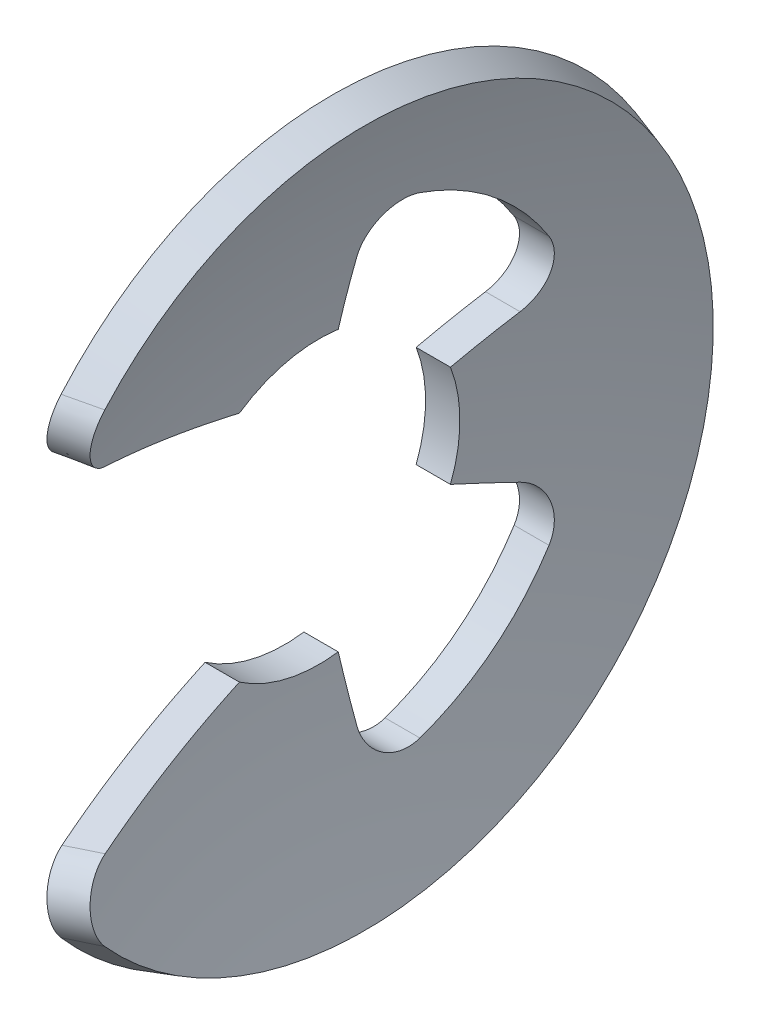
SolidWorks part; units mm, degrees
material "Cast Carbon Steel"
ref_plane "Front" through (0, 0, 0) normal (0, 0, 1) x (1, 0, 0)
ref_plane "Top" through (0, 0, 0) normal (0, 1, 0) x (1, 0, 0)
ref_plane "Right" through (0, 0, 0) normal (1, 0, 0) x (0, 0, -1)
sketch "Sketch2" plane through (0, 0, 0) normal (0, 1, 0) x (1, 0, 0)
  line L0 (0.4113, 6.6929) -> (1.016, 6.4991)
  line L1 (0, 0) -> (-0.635, 0)
  line L2 (1.016, 6.4991) -> (21.2946, 0) construction
  line L3 (0, 0) -> (21.2946, 0) construction
  arc A0 (0, 0) -> (1.016, 6.4991) centre (21.2946, 0) cw
  arc A1 (-0.635, 0) -> (0.4113, 6.6929) centre (21.2946, 0) cw
  dimension "OD" = 13.3858
revolve "Revolve1" add sketch "Sketch2" angle 360 about L3
ref_plane "Plane1" through (1.016, 0, 0) normal (1, 0, 0) x (0, 0, -1)
sketch "Sketch1" plane through (1.016, 0, 0) normal (1, 0, 0) x (0, 0, -1)
  line L0 (-5.7119, -3.4884) -> (-1.4819, -2.1714)
  line L1 (-5.7119, 3.4884) -> (-1.4819, 2.1714)
  line L2 (0.3608, -2.604) -> (0.6396, -4.6168)
  line L3 (0.3608, 2.604) -> (0.6396, 4.6168)
  line L4 (2.4526, -0.9464) -> (4.3484, -1.6779)
  line L5 (2.4526, 0.9464) -> (4.3484, 1.6779)
  line L6 (0, 0) -> (-6.6929, 0) construction
  circle A0 centre (0, 0) radius 6.6929 construction
  circle A1 centre (0, 0) radius 6.858 construction
  circle A2 centre (0, 0) radius 2.6289 construction
  arc A3 (-5.7119, -3.4884) -> (-5.7119, 3.4884) centre (0, 0) ccw construction
  arc A4 (-1.4819, -2.1714) -> (0.3608, -2.604) centre (0, 0) ccw
  arc A5 (-1.4819, 2.1714) -> (0.3608, 2.604) centre (0, 0) cw
  arc A6 (2.4526, 0.9464) -> (2.4526, -0.9464) centre (0, 0) cw
  arc A7 (0.6396, -4.6168) -> (4.3484, -1.6779) centre (0, 0) ccw
  arc A8 (4.3484, 1.6779) -> (0.6396, 4.6168) centre (0, 0) ccw
  arc A9 (-5.7119, -3.4884) -> (-5.7119, 3.4884) centre (0, 0) cw
  dimension "D" = 5.2578
  dimension "D1" = 4.6609
  dimension "D2" = 4.732
  dimension "D4" = 1.8928
  dimension "D3" = 1.8928
extrude "Cut-Extrude1" cut sketch "Sketch1" against normal through all
fillet "Fillet1" radius 0.762 6 edges at (0.1912, 4.6168, -0.6396) (0.1912, 1.6779, -4.3484) (0.1912, -1.6779, -4.3484) (0.1912, -4.6168, -0.6396)
sketch "Sketch3" plane through (0, 0, 0) normal (0, 1, 0) x (1, 0, 0)
  line L0 (0.5588, 3.175) -> (0.5588, 2.667)
  line L1 (0.5588, 2.667) -> (-0.635, 2.667)
  line L2 (-0.635, 2.667) -> (-0.635, 3.175)
  line L3 (-0.635, 3.175) -> (-8.3947, 3.175)
  line L4 (3.5433, 0) -> (3.5433, 2.921)
  line L5 (-8.3947, 3.175) -> (-8.3947, 0)
  line L6 (-8.3947, 0) -> (3.5433, 0)
  line L7 (0, 0) -> (21.2946, 0) construction
  line L8 (3.5433, 0) -> (3.5433, 3.175) construction
  line L9 (3.5433, 3.175) -> (0.5588, 3.175) construction
  line L10 (3.5433, 0) -> (17.2631, 0) construction
  line L11 (3.5433, 2.921) -> (3.2893, 3.175)
  line L12 (3.2893, 3.175) -> (0.5588, 3.175)
  point P2 (0.5588, 2.921)
  dimension "D2" = 11.938
  dimension "D1" = 2.9845
  dimension "D3" = 45
revolve "Revolve2" [suppressed] add sketch "Sketch3" angle 360 about L3
sketch "Sketch6" plane through (1.016, 0, 0) normal (1, 0, 0) x (0, 0, -1)
  line L0 (0, 6.6929) -> (0, -6.6929) construction
  arc A0 (-5.0548, -4.3868) -> (-5.0548, 4.3868) centre (0, 0) ccw construction
equation "\"D2@Sketch3\" = \"W@Sketch3\"*10"
equation "\"D1@Sketch3\" = \"D2@Sketch3\"/4"
equation "\"D1@Sketch1\" = (\"OD@Sketch2\"+\"D@Sketch1\")/4"
equation "\"D2@Sketch1\" = \"D@Sketch1\"*.9"
equation "\"D4@Sketch1\" = \"D2@Sketch1\"/2.5"
equation "\"D3@Sketch1\" = \"D4@Sketch1\""
